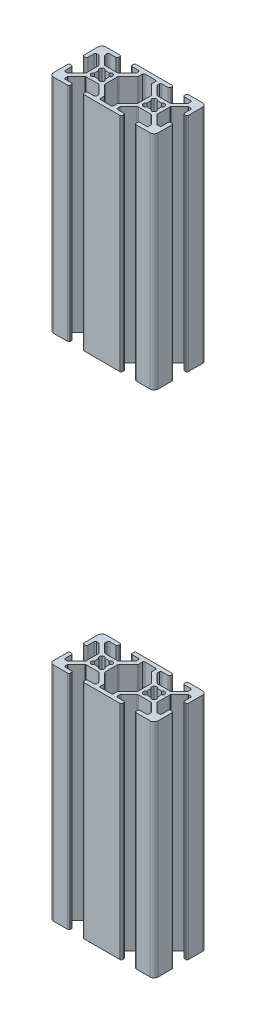
SolidWorks part; units mm, degrees
ref_plane "前视基准面" through (0, 0, 0) normal (0, 0, 1) x (1, 0, 0)
ref_plane "上视基准面" through (0, 0, 0) normal (0, 1, 0) x (1, 0, 0)
ref_plane "右视基准面" through (0, 0, 0) normal (1, 0, 0) x (0, 0, -1)
other "Configuration Table"
sketch "草图1" plane through (0, 0, 0) normal (0, 1, 0) x (1, 0, 0)
  line L0 (17.2471, 7.2074) -> (17.0675, 7.387)
  line L5 (17.0675, 11.6368) -> (17.2471, 11.8164)
  line L6 (21.4969, 11.8164) -> (21.6765, 11.6368)
  line L7 (21.6765, 7.387) -> (21.4969, 7.2074)
  line L8 (6.867, 1.5199) -> (6.867, 2.8671)
  line L9 (6.7182, 3.2263) -> (3.1758, 6.7687)
  line L10 (3.027, 7.128) -> (3.027, 11.8958)
  line L11 (3.1758, 12.255) -> (6.7182, 15.7974)
  line L26 (6.867, 16.1566) -> (6.867, 17.5039)
  line L41 (7.375, 18.0119) -> (11.369, 18.0119)
  line L56 (11.877, 17.5039) -> (11.877, 16.1566)
  line L71 (12.0258, 15.7974) -> (15.5682, 12.255)
  line L72 (15.717, 11.8958) -> (15.717, 7.128)
  line L73 (15.5682, 6.7687) -> (12.0258, 3.2263)
  line L74 (11.877, 2.8671) -> (11.877, 1.5199)
  line L75 (11.369, 1.0119) -> (7.375, 1.0119)
  line L76 (-2.7529, 7.2074) -> (-2.9325, 7.387)
  line L77 (-2.9325, 11.6368) -> (-2.7529, 11.8164)
  line L78 (1.4969, 11.8164) -> (1.6765, 11.6368)
  line L79 (1.6765, 7.387) -> (1.4969, 7.2074)
  line L80 (-3.0119, 5.8569) -> (1.7559, 5.8569)
  line L81 (2.1151, 5.7081) -> (5.2182, 2.605)
  line L82 (5.367, 2.2458) -> (5.367, 1.5199)
  line L83 (4.859, 1.0119) -> (2.51, 1.0119)
  line L84 (2.002, 0.5039) -> (2.002, 0.0199)
  line L85 (2.51, -0.4881) -> (16.234, -0.4881)
  line L86 (16.742, 0.0199) -> (16.742, 0.5039)
  line L87 (16.234, 1.0119) -> (13.885, 1.0119)
  line L88 (13.377, 1.5199) -> (13.377, 2.2458)
  line L89 (13.5258, 2.605) -> (16.6289, 5.7081)
  line L90 (16.9881, 5.8569) -> (21.7559, 5.8569)
  line L91 (22.1151, 5.7081) -> (25.2182, 2.605)
  line L92 (25.367, 2.2458) -> (25.367, 1.5199)
  line L93 (24.859, 1.0119) -> (22.51, 1.0119)
  line L94 (22.002, 0.5039) -> (22.002, 0.0199)
  line L95 (22.51, -0.4881) -> (27.872, -0.4881)
  line L96 (29.372, 1.0119) -> (29.372, 6.3739)
  line L97 (28.864, 6.8819) -> (28.38, 6.8819)
  line L98 (27.872, 6.3739) -> (27.872, 4.0249)
  line L99 (27.364, 3.5169) -> (26.6381, 3.5169)
  line L100 (26.2789, 3.6657) -> (23.1758, 6.7687)
  line L101 (23.027, 7.128) -> (23.027, 11.8958)
  line L102 (23.1758, 12.255) -> (26.2789, 15.3581)
  line L103 (26.6381, 15.5069) -> (27.364, 15.5069)
  line L104 (27.872, 14.9989) -> (27.872, 12.6499)
  line L105 (28.38, 12.1419) -> (28.864, 12.1419)
  line L106 (29.372, 12.6499) -> (29.372, 18.0119)
  line L107 (27.872, 19.5119) -> (22.51, 19.5119)
  line L108 (22.002, 19.0039) -> (22.002, 18.5199)
  line L109 (22.51, 18.0119) -> (24.859, 18.0119)
  line L110 (25.367, 17.5039) -> (25.367, 16.778)
  line L111 (25.2182, 16.4187) -> (22.1151, 13.3157)
  line L112 (21.7559, 13.1669) -> (16.9881, 13.1669)
  line L113 (16.6289, 13.3157) -> (13.5258, 16.4187)
  line L114 (13.377, 16.778) -> (13.377, 17.5039)
  line L115 (13.885, 18.0119) -> (16.234, 18.0119)
  line L116 (16.742, 18.5199) -> (16.742, 19.0039)
  line L117 (16.234, 19.5119) -> (2.51, 19.5119)
  line L118 (2.002, 19.0039) -> (2.002, 18.5199)
  line L119 (2.51, 18.0119) -> (4.859, 18.0119)
  line L120 (5.367, 17.5039) -> (5.367, 16.778)
  line L121 (5.2182, 16.4187) -> (2.1151, 13.3157)
  line L122 (1.7559, 13.1669) -> (-3.0119, 13.1669)
  line L123 (-3.3711, 13.3157) -> (-6.4742, 16.4187)
  line L124 (-6.623, 16.778) -> (-6.623, 17.5039)
  line L125 (-6.115, 18.0119) -> (-3.766, 18.0119)
  line L126 (-3.258, 18.5199) -> (-3.258, 19.0039)
  line L127 (-3.766, 19.5119) -> (-9.128, 19.5119)
  line L128 (-10.628, 18.0119) -> (-10.628, 12.6499)
  line L129 (-10.12, 12.1419) -> (-9.636, 12.1419)
  line L130 (-9.128, 12.6499) -> (-9.128, 14.9989)
  line L131 (-8.62, 15.5069) -> (-7.8941, 15.5069)
  line L132 (-7.5349, 15.3581) -> (-4.4318, 12.255)
  line L133 (-4.283, 11.8958) -> (-4.283, 7.128)
  line L134 (-4.4318, 6.7687) -> (-7.5349, 3.6657)
  line L135 (-7.8941, 3.5169) -> (-8.62, 3.5169)
  line L136 (-9.128, 4.0249) -> (-9.128, 6.3739)
  line L137 (-9.636, 6.8819) -> (-10.12, 6.8819)
  line L138 (-10.628, 6.3739) -> (-10.628, 1.0119)
  line L139 (-9.128, -0.4881) -> (-3.766, -0.4881)
  line L140 (-3.258, 0.0199) -> (-3.258, 0.5039)
  line L141 (-3.766, 1.0119) -> (-6.115, 1.0119)
  line L142 (-6.623, 1.5199) -> (-6.623, 2.2458)
  line L143 (-6.4742, 2.605) -> (-3.3711, 5.7081)
  arc A5 (17.4369, 8.7079) -> (17.0675, 7.387) centre (17.624, 7.9435) ccw
  arc A6 (17.4369, 10.3158) -> (17.4369, 8.7079) centre (19.372, 9.5119) ccw
  arc A7 (17.0675, 11.6368) -> (17.4369, 10.3158) centre (17.624, 11.0803) ccw
  arc A8 (18.568, 11.447) -> (17.2471, 11.8164) centre (17.8036, 11.2599) ccw
  arc A9 (20.176, 11.447) -> (18.568, 11.447) centre (19.372, 9.5119) ccw
  arc A10 (21.4969, 11.8164) -> (20.176, 11.447) centre (20.9404, 11.2599) ccw
  arc A11 (21.3071, 10.3158) -> (21.6765, 11.6368) centre (21.12, 11.0803) ccw
  arc A12 (21.3071, 8.7079) -> (21.3071, 10.3158) centre (19.372, 9.5119) ccw
  arc A13 (21.6765, 7.387) -> (21.3071, 8.7079) centre (21.12, 7.9435) ccw
  arc A14 (20.176, 7.5767) -> (21.4969, 7.2074) centre (20.9404, 7.7639) ccw
  arc A15 (18.568, 7.5767) -> (20.176, 7.5767) centre (19.372, 9.5119) ccw
  arc A16 (17.2471, 7.2074) -> (18.568, 7.5767) centre (17.8036, 7.7639) ccw
  arc A17 (6.867, 1.5199) -> (7.375, 1.0119) centre (7.375, 1.5199) ccw
  arc A18 (6.867, 2.8671) -> (6.7182, 3.2263) centre (6.359, 2.8671) ccw
  arc A19 (3.027, 7.128) -> (3.1758, 6.7687) centre (3.535, 7.128) ccw
  arc A20 (3.1758, 12.255) -> (3.027, 11.8958) centre (3.535, 11.8958) ccw
  arc A21 (6.7182, 15.7974) -> (6.867, 16.1566) centre (6.359, 16.1566) ccw
  arc A22 (7.375, 18.0119) -> (6.867, 17.5039) centre (7.375, 17.5039) ccw
  arc A23 (11.877, 17.5039) -> (11.369, 18.0119) centre (11.369, 17.5039) ccw
  arc A24 (11.877, 16.1566) -> (12.0258, 15.7974) centre (12.385, 16.1566) ccw
  arc A25 (15.717, 11.8958) -> (15.5682, 12.255) centre (15.209, 11.8958) ccw
  arc A26 (15.5682, 6.7687) -> (15.717, 7.128) centre (15.209, 7.128) ccw
  arc A27 (12.0258, 3.2263) -> (11.877, 2.8671) centre (12.385, 2.8671) ccw
  arc A28 (11.369, 1.0119) -> (11.877, 1.5199) centre (11.369, 1.5199) ccw
  arc A29 (-2.5631, 8.7079) -> (-2.9325, 7.387) centre (-2.376, 7.9435) ccw
  arc A30 (-2.5631, 10.3158) -> (-2.5631, 8.7079) centre (-0.628, 9.5119) ccw
  arc A31 (-2.9325, 11.6368) -> (-2.5631, 10.3158) centre (-2.376, 11.0803) ccw
  arc A32 (-1.432, 11.447) -> (-2.7529, 11.8164) centre (-2.1964, 11.2599) ccw
  arc A33 (0.176, 11.447) -> (-1.432, 11.447) centre (-0.628, 9.5119) ccw
  arc A34 (1.4969, 11.8164) -> (0.176, 11.447) centre (0.9404, 11.2599) ccw
  arc A35 (1.3071, 10.3158) -> (1.6765, 11.6368) centre (1.12, 11.0803) ccw
  arc A36 (1.3071, 8.7079) -> (1.3071, 10.3158) centre (-0.628, 9.5119) ccw
  arc A37 (1.6765, 7.387) -> (1.3071, 8.7079) centre (1.12, 7.9435) ccw
  arc A38 (0.176, 7.5767) -> (1.4969, 7.2074) centre (0.9404, 7.7639) ccw
  arc A39 (-1.432, 7.5767) -> (0.176, 7.5767) centre (-0.628, 9.5119) ccw
  arc A40 (-2.7529, 7.2074) -> (-1.432, 7.5767) centre (-2.1964, 7.7639) ccw
  arc A41 (-3.0119, 5.8569) -> (-3.3711, 5.7081) centre (-3.0119, 5.3489) ccw
  arc A42 (2.1151, 5.7081) -> (1.7559, 5.8569) centre (1.7559, 5.3489) ccw
  arc A43 (5.367, 2.2458) -> (5.2182, 2.605) centre (4.859, 2.2458) ccw
  arc A44 (4.859, 1.0119) -> (5.367, 1.5199) centre (4.859, 1.5199) ccw
  arc A45 (2.51, 1.0119) -> (2.002, 0.5039) centre (2.51, 0.5039) ccw
  arc A46 (2.002, 0.0199) -> (2.51, -0.4881) centre (2.51, 0.0199) ccw
  arc A47 (16.234, -0.4881) -> (16.742, 0.0199) centre (16.234, 0.0199) ccw
  arc A48 (16.742, 0.5039) -> (16.234, 1.0119) centre (16.234, 0.5039) ccw
  arc A49 (13.377, 1.5199) -> (13.885, 1.0119) centre (13.885, 1.5199) ccw
  arc A50 (13.5258, 2.605) -> (13.377, 2.2458) centre (13.885, 2.2458) ccw
  arc A51 (16.9881, 5.8569) -> (16.6289, 5.7081) centre (16.9881, 5.3489) ccw
  arc A52 (22.1151, 5.7081) -> (21.7559, 5.8569) centre (21.7559, 5.3489) ccw
  arc A53 (25.367, 2.2458) -> (25.2182, 2.605) centre (24.859, 2.2458) ccw
  arc A54 (24.859, 1.0119) -> (25.367, 1.5199) centre (24.859, 1.5199) ccw
  arc A55 (22.51, 1.0119) -> (22.002, 0.5039) centre (22.51, 0.5039) ccw
  arc A56 (22.002, 0.0199) -> (22.51, -0.4881) centre (22.51, 0.0199) ccw
  arc A57 (27.872, -0.4881) -> (29.372, 1.0119) centre (27.872, 1.0119) ccw
  arc A58 (29.372, 6.3739) -> (28.864, 6.8819) centre (28.864, 6.3739) ccw
  arc A59 (28.38, 6.8819) -> (27.872, 6.3739) centre (28.38, 6.3739) ccw
  arc A60 (27.364, 3.5169) -> (27.872, 4.0249) centre (27.364, 4.0249) ccw
  arc A61 (26.2789, 3.6657) -> (26.6381, 3.5169) centre (26.6381, 4.0249) ccw
  arc A62 (23.027, 7.128) -> (23.1758, 6.7687) centre (23.535, 7.128) ccw
  arc A63 (23.1758, 12.255) -> (23.027, 11.8958) centre (23.535, 11.8958) ccw
  arc A64 (26.6381, 15.5069) -> (26.2789, 15.3581) centre (26.6381, 14.9989) ccw
  arc A65 (27.872, 14.9989) -> (27.364, 15.5069) centre (27.364, 14.9989) ccw
  arc A66 (27.872, 12.6499) -> (28.38, 12.1419) centre (28.38, 12.6499) ccw
  arc A67 (28.864, 12.1419) -> (29.372, 12.6499) centre (28.864, 12.6499) ccw
  arc A68 (29.372, 18.0119) -> (27.872, 19.5119) centre (27.872, 18.0119) ccw
  arc A69 (22.51, 19.5119) -> (22.002, 19.0039) centre (22.51, 19.0039) ccw
  arc A70 (22.002, 18.5199) -> (22.51, 18.0119) centre (22.51, 18.5199) ccw
  arc A71 (25.367, 17.5039) -> (24.859, 18.0119) centre (24.859, 17.5039) ccw
  arc A72 (25.2182, 16.4187) -> (25.367, 16.778) centre (24.859, 16.778) ccw
  arc A73 (21.7559, 13.1669) -> (22.1151, 13.3157) centre (21.7559, 13.6749) ccw
  arc A74 (16.6289, 13.3157) -> (16.9881, 13.1669) centre (16.9881, 13.6749) ccw
  arc A75 (13.377, 16.778) -> (13.5258, 16.4187) centre (13.885, 16.778) ccw
  arc A76 (13.885, 18.0119) -> (13.377, 17.5039) centre (13.885, 17.5039) ccw
  arc A77 (16.234, 18.0119) -> (16.742, 18.5199) centre (16.234, 18.5199) ccw
  arc A78 (16.742, 19.0039) -> (16.234, 19.5119) centre (16.234, 19.0039) ccw
  arc A79 (2.51, 19.5119) -> (2.002, 19.0039) centre (2.51, 19.0039) ccw
  arc A80 (2.002, 18.5199) -> (2.51, 18.0119) centre (2.51, 18.5199) ccw
  arc A81 (5.367, 17.5039) -> (4.859, 18.0119) centre (4.859, 17.5039) ccw
  arc A82 (5.2182, 16.4187) -> (5.367, 16.778) centre (4.859, 16.778) ccw
  arc A83 (1.7559, 13.1669) -> (2.1151, 13.3157) centre (1.7559, 13.6749) ccw
  arc A84 (-3.3711, 13.3157) -> (-3.0119, 13.1669) centre (-3.0119, 13.6749) ccw
  arc A85 (-6.623, 16.778) -> (-6.4742, 16.4187) centre (-6.115, 16.778) ccw
  arc A86 (-6.115, 18.0119) -> (-6.623, 17.5039) centre (-6.115, 17.5039) ccw
  arc A87 (-3.766, 18.0119) -> (-3.258, 18.5199) centre (-3.766, 18.5199) ccw
  arc A88 (-3.258, 19.0039) -> (-3.766, 19.5119) centre (-3.766, 19.0039) ccw
  arc A89 (-9.128, 19.5119) -> (-10.628, 18.0119) centre (-9.128, 18.0119) ccw
  arc A90 (-10.628, 12.6499) -> (-10.12, 12.1419) centre (-10.12, 12.6499) ccw
  arc A91 (-9.636, 12.1419) -> (-9.128, 12.6499) centre (-9.636, 12.6499) ccw
  arc A92 (-8.62, 15.5069) -> (-9.128, 14.9989) centre (-8.62, 14.9989) ccw
  arc A93 (-7.5349, 15.3581) -> (-7.8941, 15.5069) centre (-7.8941, 14.9989) ccw
  arc A94 (-4.283, 11.8958) -> (-4.4318, 12.255) centre (-4.791, 11.8958) ccw
  arc A95 (-4.4318, 6.7687) -> (-4.283, 7.128) centre (-4.791, 7.128) ccw
  arc A96 (-7.8941, 3.5169) -> (-7.5349, 3.6657) centre (-7.8941, 4.0249) ccw
  arc A97 (-9.128, 4.0249) -> (-8.62, 3.5169) centre (-8.62, 4.0249) ccw
  arc A98 (-9.128, 6.3739) -> (-9.636, 6.8819) centre (-9.636, 6.3739) ccw
  arc A99 (-10.12, 6.8819) -> (-10.628, 6.3739) centre (-10.12, 6.3739) ccw
  arc A100 (-10.628, 1.0119) -> (-9.128, -0.4881) centre (-9.128, 1.0119) ccw
  arc A101 (-3.766, -0.4881) -> (-3.258, 0.0199) centre (-3.766, 0.0199) ccw
  arc A102 (-3.258, 0.5039) -> (-3.766, 1.0119) centre (-3.766, 0.5039) ccw
  arc A103 (-6.623, 1.5199) -> (-6.115, 1.0119) centre (-6.115, 1.5199) ccw
  arc A104 (-6.4742, 2.605) -> (-6.623, 2.2458) centre (-6.115, 2.2458) ccw
extrude "凸台-拉伸1" add sketch "草图1" along normal mid plane 280
sketch "草图2" plane through (0, 0, -19.5119) normal (0, 0, -1) x (-1, 0, 0)
  line L0 (-29.372, 140) -> (-29.372, -140) construction
  line L1 (-29.372, 55) -> (10.628, 55)
  line L2 (-29.372, 55) -> (-29.372, -55)
  line L3 (-29.372, -55) -> (10.628, -55)
  line L4 (10.628, 55) -> (10.628, -55)
  line L5 (10.628, 140) -> (10.628, -140) construction
  line L6 (-16.234, 140) -> (-2.51, 140) construction
  line L7 (-16.234, -140) -> (-2.51, -140) construction
  dimension "D1" = 40
  dimension "D2" = 85
  dimension "D3" = 85
extrude "切除-拉伸1" cut sketch "草图2" against normal blind 32
